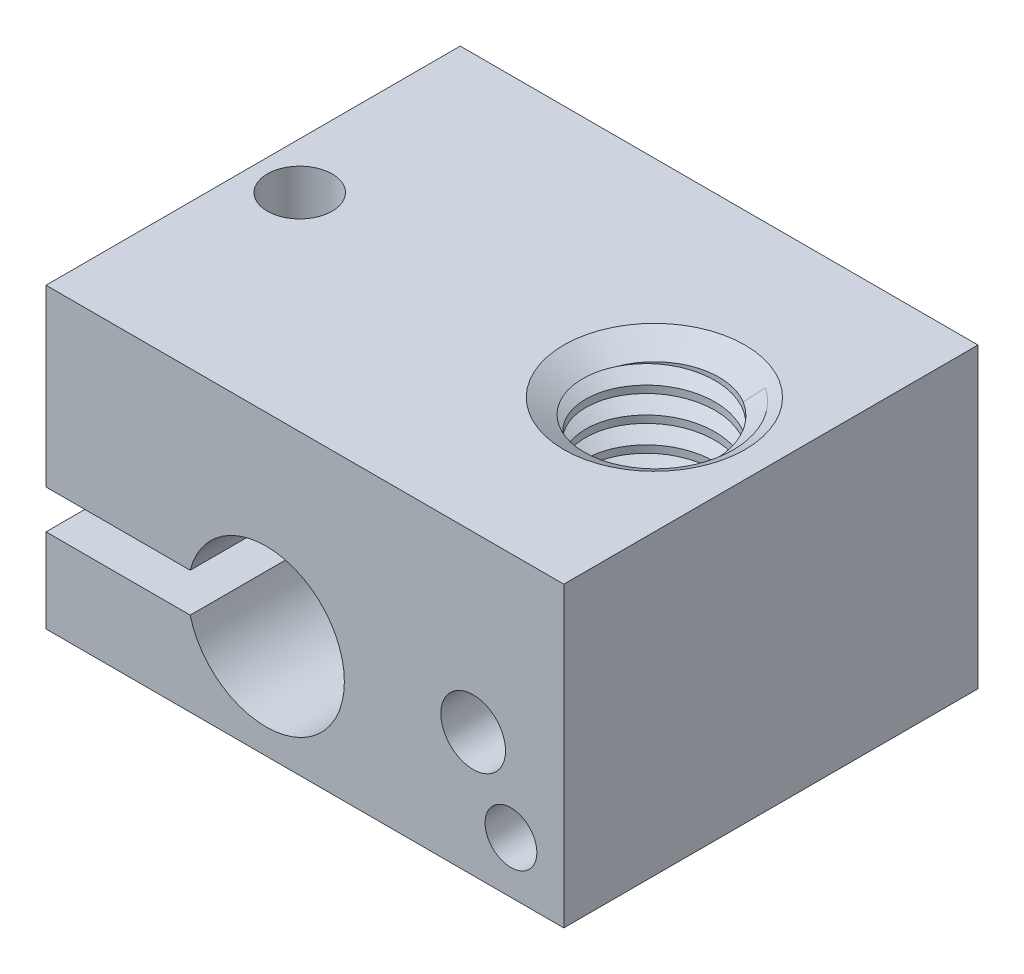
SolidWorks part; units mm, degrees
material "Copper"
ref_plane "Front Plane" through (0, 0, 0) normal (0, 0, 1) x (1, 0, 0)
ref_plane "Top Plane" through (0, 0, 0) normal (0, 1, 0) x (1, 0, 0)
ref_plane "Right Plane" through (0, 0, 0) normal (1, 0, 0) x (0, 0, -1)
sketch "Sketch1" plane through (0, 0, 0) normal (0, 1, 0) x (1, 0, 0)
  line L1 (10, 8) -> (-10, 8)
  line L2 (10, 8) -> (10, -8)
  line L3 (10, -8) -> (-10, -8)
  line L4 (-10, 8) -> (-10, -8)
  line L5 (10, 8) -> (-10, -8) construction
  line L6 (10, -8) -> (-10, 8) construction
  point P0 (0, 0)
  dimension "D1" = 20
  dimension "D2" = 16
extrude "Boss-Extrude1" add sketch "Sketch1" along normal mid plane 11.5
sketch "Sketch2" plane through (0, 5.75, 0) normal (0, 1, 0) x (1, 0, 0)
  line L0 (0, 8) -> (0, -8) construction
  line L1 (10, 8) -> (-10, 8) construction
  line L2 (-10, -8) -> (10, -8) construction
  line L3 (-10, 0) -> (10, 0) construction
  line L4 (-10, 8) -> (-10, -8) construction
  line L5 (10, -8) -> (10, 8) construction
  circle A0 centre (5.5, 0) radius 2.5
  circle A1 centre (-8.2, 0) radius 1.25
  dimension "D1" = 5
  dimension "D4" = 2.5
  dimension "D2" = 4.5
  dimension "D3" = 1.8
extrude "Cut-Extrude1" cut sketch "Sketch2" against normal up to next
sketch "Sketch3" plane through (0, 0, 8) normal (0, 0, 1) x (1, 0, 0)
  line L0 (0, 0) -> (-18.9264, 0) construction
  line L1 (-18.9264, 0) -> (-18.9264, -4.2761) construction
  line L2 (-18.9264, -4.2761) -> (0, -4.2761) construction
  line L3 (0, -4.2761) -> (0, 0) construction
  line L4 (0, -1.75) -> (-17.234, -1.75) construction
  line L5 (-10, -5.75) -> (10, -5.75) construction
  line L6 (-15.1475, -1.75) -> (-15.1475, -1)
  line L7 (-15.1475, -1) -> (-4.4306, -1)
  line L9 (-15.1475, -1.75) -> (-15.1475, -2.5)
  line L10 (-15.1475, -2.5) -> (-4.4306, -2.5)
  line L11 (10, 5.75) -> (10, -5.75) construction
  arc A0 (-4.4306, -1) -> (-4.4306, -2.5) centre (-1.5, -1.75) cw
  dimension "D2" = 3.025
  dimension "D1" = 4
  dimension "D3" = 11.5
  dimension "D4" = 0.75
  dimension "D5" = 0.75
extrude "Cut-Extrude2" cut sketch "Sketch3" against normal up to next
sketch "Sketch4" plane through (0, 0, 8) normal (0, 0, 1) x (1, 0, 0)
  line L0 (2.5543, -3.75) -> (13.3659, -3.75) construction
  line L1 (13.3659, -3.75) -> (13.3659, -0.95) construction
  line L2 (13.3659, -0.95) -> (5.608, -0.95) construction
  line L3 (-10, -5.75) -> (10, -5.75) construction
  line L4 (8, -5.75) -> (8, 1.0186) construction
  line L5 (8, 1.0186) -> (6.5, 1.0186) construction
  line L6 (6.5, 1.0186) -> (6.5, -5.75) construction
  line L7 (10, 5.75) -> (10, -5.75) construction
  circle A0 centre (7.9601, -3.75) radius 1
  circle A1 centre (6.5, -0.95) radius 1.25
  dimension "D5" = 2
  dimension "D6" = 2.5
  dimension "D1" = 2
  dimension "D2" = 4.8
  dimension "D3" = 2
  dimension "D4" = 3.5
extrude "Cut-Extrude3" cut sketch "Sketch4" against normal blind 3.4
sketch "Sketch5" plane through (0, 0, 8) normal (0, 0, 1) x (1, 0, 0)
  circle A0 centre (7.9601, -3.75) radius 0.8
  dimension "D1" = 1.6
extrude "Cut-Extrude4" cut sketch "Sketch5" against normal blind 4.4
ref_plane "Plane1" through (0, 8.75, 0) normal (0, 1, 0) x (1, 0, 0)
sketch "Sketch6" plane through (0, 8.75, 0) normal (0, 1, 0) x (1, 0, 0)
  circle A0 centre (5.5, 0) radius 2.5 construction
  circle A1 centre (5.5, 0) radius 2.5 construction
  circle A2 centre (5.5, 0) radius 3.125
  dimension "D1" = 6.25
curve "Helix/Spiral1" pitch 1 height 20 radius 3.125 centre (5.5, 8.75, 0) axis (0, -1, 0) start towards (0, 0, 1)
chamfer "Chamfer1" distance 1 angle 30 1 edges at (5.5, 5.75, 2.5) first distance on face at (-8.2, 5.75, 1.25)
sketch "Sketch7" plane through (0, 0, 0) normal (0, 0, 1) x (1, 0, 0)
  line L0 (8.6229, 6.3692) -> (6.1425, 6.3692) construction
  line L1 (8.6229, 6.3692) -> (7.7482, 6.8742)
  line L2 (7.7482, 6.8742) -> (7.7482, 5.8642)
  line L3 (8.6229, 6.3692) -> (7.7482, 5.8642)
  spline S0 degree 3 poles (3.2903, 8.75) (3.5777, 8.7293) (4.2738, 8.6874) (5.4998, 8.625) (6.7271, 8.5625) (7.7672, 8.5) (8.4623, 8.4375) (8.7064, 8.375) (8.4623, 8.3125) (7.7672, 8.25) (6.727, 8.1875) (5.5, 8.125) (4.273, 8.0625) (3.2328, 8) (2.5377, 7.9375) (2.2936, 7.875) (2.5377, 7.8125) (3.2328, 7.75) (4.273, 7.6875) (5.5, 7.625) (6.727, 7.5625) (7.7672, 7.5) (8.4623, 7.4375) (8.7064, 7.375) (8.4623, 7.3125) (7.7672, 7.25) (6.727, 7.1875) (5.5, 7.125) (4.273, 7.0625) (3.2328, 7) (2.5377, 6.9375) (2.2936, 6.875) (2.5377, 6.8125) (3.2328, 6.75) (4.273, 6.6875) (5.5, 6.625) (6.727, 6.5625) (7.7672, 6.5) (8.4623, 6.4375) (8.7064, 6.375) (8.4623, 6.3125) (7.7672, 6.25) (6.727, 6.1875) (5.5, 6.125) (4.273, 6.0625) (3.2328, 6) (2.5377, 5.9375) (2.2936, 5.875) (2.5377, 5.8125) (3.2328, 5.75) (4.273, 5.6875) (5.5, 5.625) (6.727, 5.5625) (7.7672, 5.5) (8.4623, 5.4375) (8.7064, 5.375) (8.4623, 5.3125) (7.7672, 5.25) (6.727, 5.1875) (5.5, 5.125) (4.273, 5.0625) (3.2328, 5) (2.5377, 4.9375) (2.2936, 4.875) (2.5377, 4.8125) (3.2328, 4.75) (4.273, 4.6875) (5.5, 4.625) (6.727, 4.5625) (7.7672, 4.5) (8.4623, 4.4375) (8.7064, 4.375) (8.4623, 4.3125) (7.7672, 4.25) (6.727, 4.1875) (5.5, 4.125) (4.273, 4.0625) (3.2328, 4) (2.5377, 3.9375) (2.2936, 3.875) (2.5377, 3.8125) (3.2328, 3.75) (4.273, 3.6875) (5.5, 3.625) (6.727, 3.5625) (7.7672, 3.5) (8.4623, 3.4375) (8.7064, 3.375) (8.4623, 3.3125) (7.7672, 3.25) (6.727, 3.1875) (5.5, 3.125) (4.273, 3.0625) (3.2328, 3) (2.5377, 2.9375) (2.2936, 2.875) (2.5377, 2.8125) (3.2328, 2.75) (4.273, 2.6875) (5.5, 2.625) (6.727, 2.5625) (7.7672, 2.5) (8.4623, 2.4375) (8.7064, 2.375) (8.4623, 2.3125) (7.7672, 2.25) (6.727, 2.1875) (5.5, 2.125) (4.273, 2.0625) (3.2328, 2) (2.5377, 1.9375) (2.2936, 1.875) (2.5377, 1.8125) (3.2328, 1.75) (4.273, 1.6875) (5.5, 1.625) (6.727, 1.5625) (7.7672, 1.5) (8.4623, 1.4375) (8.7064, 1.375) (8.4623, 1.3125) (7.7672, 1.25) (6.727, 1.1875) (5.5, 1.125) (4.273, 1.0625) (3.2328, 1) (2.5377, 0.9375) (2.2936, 0.875) (2.5377, 0.8125) (3.2328, 0.75) (4.273, 0.6875) (5.5, 0.625) (6.727, 0.5625) (7.7672, 0.5) (8.4623, 0.4375) (8.7064, 0.375) (8.4623, 0.3125) (7.7672, 0.25) (6.727, 0.1875) (5.5, 0.125) (4.273, 0.0625) (3.2328, 0) (2.5377, -0.0625) (2.2936, -0.125) (2.5377, -0.1875) (3.2328, -0.25) (4.273, -0.3125) (5.5, -0.375) (6.727, -0.4375) (7.7672, -0.5) (8.4623, -0.5625) (8.7064, -0.625) (8.4623, -0.6875) (7.7672, -0.75) (6.727, -0.8125) (5.5, -0.875) (4.273, -0.9375) (3.2328, -1) (2.5377, -1.0625) (2.2936, -1.125) (2.5377, -1.1875) (3.2328, -1.25) (4.273, -1.3125) (5.5, -1.375) (6.727, -1.4375) (7.7672, -1.5) (8.4623, -1.5625) (8.7064, -1.625) (8.4623, -1.6875) (7.7672, -1.75) (6.727, -1.8125) (5.5, -1.875) (4.273, -1.9375) (3.2328, -2) (2.5377, -2.0625) (2.2936, -2.125) (2.5377, -2.1875) (3.2328, -2.25) (4.273, -2.3125) (5.5, -2.375) (6.727, -2.4375) (7.7672, -2.5) (8.4623, -2.5625) (8.7064, -2.625) (8.4623, -2.6875) (7.7672, -2.75) (6.727, -2.8125) (5.5, -2.875) (4.273, -2.9375) (3.2328, -3) (2.5377, -3.0625) (2.2936, -3.125) (2.5377, -3.1875) (3.2328, -3.25) (4.273, -3.3125) (5.5, -3.375) (6.727, -3.4375) (7.7672, -3.5) (8.4623, -3.5625) (8.7064, -3.625) (8.4623, -3.6875) (7.7672, -3.75) (6.727, -3.8125) (5.5, -3.875) (4.273, -3.9375) (3.2328, -4) (2.5377, -4.0625) (2.2936, -4.125) (2.5377, -4.1875) (3.2328, -4.25) (4.273, -4.3125) (5.5, -4.375) (6.727, -4.4375) (7.7672, -4.5) (8.4623, -4.5625) (8.7064, -4.625) (8.4623, -4.6875) (7.7672, -4.75) (6.727, -4.8125) (5.5, -4.875) (4.273, -4.9375) (3.2328, -5) (2.5377, -5.0625) (2.2936, -5.125) (2.5377, -5.1875) (3.2328, -5.25) (4.273, -5.3125) (5.5, -5.375) (6.727, -5.4375) (7.7672, -5.5) (8.4623, -5.5625) (8.7064, -5.625) (8.4623, -5.6875) (7.7672, -5.75) (6.727, -5.8125) (5.5, -5.875) (4.273, -5.9375) (3.2328, -6) (2.5377, -6.0625) (2.2936, -6.125) (2.5377, -6.1875) (3.2328, -6.25) (4.273, -6.3125) (5.5, -6.375) (6.727, -6.4375) (7.7672, -6.5) (8.4623, -6.5625) (8.7064, -6.625) (8.4623, -6.6875) (7.7672, -6.75) (6.727, -6.8125) (5.5, -6.875) (4.273, -6.9375) (3.2328, -7) (2.5377, -7.0625) (2.2936, -7.125) (2.5377, -7.1875) (3.2328, -7.25) (4.273, -7.3125) (5.5, -7.375) (6.727, -7.4375) (7.7672, -7.5) (8.4623, -7.5625) (8.7064, -7.625) (8.4623, -7.6875) (7.7672, -7.75) (6.727, -7.8125) (5.5, -7.875) (4.273, -7.9375) (3.2328, -8) (2.5377, -8.0625) (2.2936, -8.125) (2.5377, -8.1875) (3.2328, -8.25) (4.273, -8.3125) (5.5, -8.375) (6.727, -8.4375) (7.7672, -8.5) (8.4623, -8.5625) (8.7064, -8.625) (8.4623, -8.6875) (7.7672, -8.75) (6.727, -8.8125) (5.5, -8.875) (4.273, -8.9375) (3.2328, -9) (2.5377, -9.0625) (2.2936, -9.125) (2.5377, -9.1875) (3.2328, -9.25) (4.273, -9.3125) (5.5, -9.375) (6.727, -9.4375) (7.7672, -9.5) (8.4623, -9.5625) (8.7064, -9.625) (8.4623, -9.6875) (7.7672, -9.75) (6.727, -9.8125) (5.5, -9.875) (4.273, -9.9375) (3.2328, -10) (2.5377, -10.0625) (2.2936, -10.125) (2.5377, -10.1875) (3.2328, -10.25) (4.273, -10.3125) (5.5, -10.375) (6.727, -10.4375) (7.7672, -10.5) (8.4623, -10.5625) (8.7064, -10.625) (8.4623, -10.6875) (7.7672, -10.75) (6.727, -10.8125) (5.5, -10.875) (4.273, -10.9375) (3.2328, -11) (2.5377, -11.0625) (2.2939, -11.125) (2.5369, -11.1874) (3.0029, -11.2293) (3.2903, -11.25) knots 0 0 0 0 0.003125 0.00625 0.009375 0.0125 0.015625 0.01875 0.021875 0.025 0.028125 0.03125 0.034375 0.0375 0.040625 0.04375 0.046875 0.05 0.053125 0.05625 0.059375 0.0625 0.065625 0.06875 0.071875 0.075 0.078125 0.08125 0.084375 0.0875 0.090625 0.09375 0.096875 0.1 0.103125 0.10625 0.109375 0.1125 0.115625 0.11875 0.121875 0.125 0.128125 0.13125 0.134375 0.1375 0.140625 0.14375 0.146875 0.15 0.153125 0.15625 0.159375 0.1625 0.165625 0.16875 0.171875 0.175 0.178125 0.18125 0.184375 0.1875 0.190625 0.19375 0.196875 0.2 0.203125 0.20625 0.209375 0.2125 0.215625 0.21875 0.221875 0.225 0.228125 0.23125 0.234375 0.2375 0.240625 0.24375 0.246875 0.25 0.253125 0.25625 0.259375 0.2625 0.265625 0.26875 0.271875 0.275 0.278125 0.28125 0.284375 0.2875 0.290625 0.29375 0.296875 0.3 0.303125 0.30625 0.309375 0.3125 0.315625 0.31875 0.321875 0.325 0.328125 0.33125 0.334375 0.3375 0.340625 0.34375 0.346875 0.35 0.353125 0.35625 0.359375 0.3625 0.365625 0.36875 0.371875 0.375 0.378125 0.38125 0.384375 0.3875 0.390625 0.39375 0.396875 0.4 0.403125 0.40625 0.409375 0.4125 0.415625 0.41875 0.421875 0.425 0.428125 0.43125 0.434375 0.4375 0.440625 0.44375 0.446875 0.45 0.453125 0.45625 0.459375 0.4625 0.465625 0.46875 0.471875 0.475 0.478125 0.48125 0.484375 0.4875 0.490625 0.49375 0.496875 0.5 0.503125 0.50625 0.509375 0.5125 0.515625 0.51875 0.521875 0.525 0.528125 0.53125 0.534375 0.5375 0.540625 0.54375 0.546875 0.55 0.553125 0.55625 0.559375 0.5625 0.565625 0.56875 0.571875 0.575 0.578125 0.58125 0.584375 0.5875 0.590625 0.59375 0.596875 0.6 0.603125 0.60625 0.609375 0.6125 0.615625 0.61875 0.621875 0.625 0.628125 0.63125 0.634375 0.6375 0.640625 0.64375 0.646875 0.65 0.653125 0.65625 0.659375 0.6625 0.665625 0.66875 0.671875 0.675 0.678125 0.68125 0.684375 0.6875 0.690625 0.69375 0.696875 0.7 0.703125 0.70625 0.709375 0.7125 0.715625 0.71875 0.721875 0.725 0.728125 0.73125 0.734375 0.7375 0.740625 0.74375 0.746875 0.75 0.753125 0.75625 0.759375 0.7625 0.765625 0.76875 0.771875 0.775 0.778125 0.78125 0.784375 0.7875 0.790625 0.79375 0.796875 0.8 0.803125 0.80625 0.809375 0.8125 0.815625 0.81875 0.821875 0.825 0.828125 0.83125 0.834375 0.8375 0.840625 0.84375 0.846875 0.85 0.853125 0.85625 0.859375 0.8625 0.865625 0.86875 0.871875 0.875 0.878125 0.88125 0.884375 0.8875 0.890625 0.89375 0.896875 0.9 0.903125 0.90625 0.909375 0.9125 0.915625 0.91875 0.921875 0.925 0.928125 0.93125 0.934375 0.9375 0.940625 0.94375 0.946875 0.95 0.953125 0.95625 0.959375 0.9625 0.965625 0.96875 0.971875 0.975 0.978125 0.98125 0.984375 0.9875 0.990625 0.99375 0.996875 1 1 1 1 construction
  point P7 (7.7482, 6.3692)
  dimension "D1" = 30
  dimension "D2" = 0.505
sweep "Cut-Sweep1" cut profiles "Sketch7" path "Helix/Spiral1" align with end faces yes
